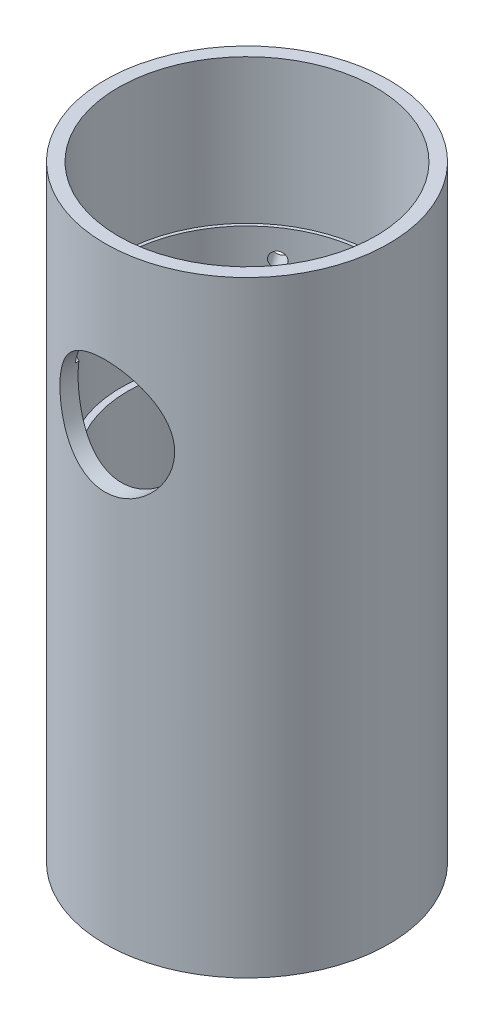
SolidWorks part; units mm, degrees
ref_plane "Front Plane" through (0, 0, 0) normal (0, 0, 1) x (1, 0, 0)
ref_plane "Top Plane" through (0, 0, 0) normal (0, 1, 0) x (1, 0, 0)
ref_plane "Right Plane" through (0, 0, 0) normal (1, 0, 0) x (0, 0, -1)
sketch "Sketch1" plane through (0, 0, 0) normal (0, 1, 0) x (1, 0, 0)
  line L0 (0, 38.25) -> (0, 43.25) construction
  circle A0 centre (0, 0) radius 38.25
  circle A1 centre (0, 0) radius 43.25
  dimension "D1" = 76.5
  dimension "D2" = 5
extrude "Boss-Extrude1" add sketch "Sketch1" along normal mid plane 185
sketch "Sketch2" plane through (0, -92.5, 0) normal (0, -1, 0) x (1, 0, 0)
  line L0 (0, 36.25) -> (0, 38.25) construction
  circle A0 centre (0, 0) radius 36.25
  circle A1 centre (0, 0) radius 38.25 construction
  circle A2 centre (0, 0) radius 38.25
  dimension "D1" = 2
extrude "Boss-Extrude2" add sketch "Sketch2" against normal blind 100 from offset 6.35 offset against normal yes
sketch "Sketch6" plane through (0, 92.5, 0) normal (0, 1, 0) x (1, 0, 0)
  line L0 (0, 38.25) -> (0, 39.25) construction
  circle A0 centre (0, 0) radius 39.25
  circle A1 centre (0, 0) radius 38.25 construction
  circle A2 centre (0, 0) radius 38.25
  dimension "D1" = 1
extrude "Cut-Extrude3" cut sketch "Sketch6" against normal blind 44
sketch "Sketch7" plane through (0, 0, 0) normal (1, 0, 0) x (0, 0, -1)
  line L0 (43.25, 92.5) -> (-43.25, 92.5) construction
  circle A0 centre (0, 44.35) radius 17.5
  dimension "D2" = 35
  dimension "D1" = 48.15
extrude "Cut-Extrude4" [suppressed] cut sketch "Sketch7" against normal through all
sketch "Sketch8" plane through (0, 0, 0) normal (0, 0, 1) x (1, 0, 0)
  line L0 (39.25, 92.5) -> (-39.25, 92.5) construction
  circle A0 centre (0, 44.35) radius 17.5
  dimension "D2" = 35
  dimension "D1" = 48.15
extrude "Cut-Extrude5" cut sketch "Sketch8" along normal through all
sketch "Sketch9" plane through (0, 0, 0) normal (0, 1, 0) x (1, 0, 0)
  line L0 (0, 0) -> (0, 43.25) construction
  line L1 (0, 0) -> (-24.8072, 35.4283) construction
  line L2 (0, 0) -> (24.8072, 35.4283) construction
  circle A0 centre (0, 0) radius 43.25 construction
  point P8 (0, 0)
  point P9 (0, 0)
  point P10 (0, 0)
  point P11 (0, 0)
  dimension "D1" = 35
ref_plane "Plane1" through (0, 0, 0) normal (-0.5736, 0, -0.8192) x (-0.8192, 0, 0.5736)
sketch "Sketch11" plane through (0, 0, 0) normal (-0.5736, 0, -0.8192) x (-0.8192, 0, 0.5736)
  line L0 (0, 0) -> (30.5818, 0) construction
  circle A0 centre (0, -40) radius 2.25
  circle A1 centre (0, 40) radius 2.25
  dimension "D1" = 4.5
  dimension "D2" = 40
extrude "Cut-Extrude6" cut sketch "Sketch11" along normal through all
mirror "Mirror1" about plane through (0, 0, 0) normal (1, 0, 0) of "Cut-Extrude6"
